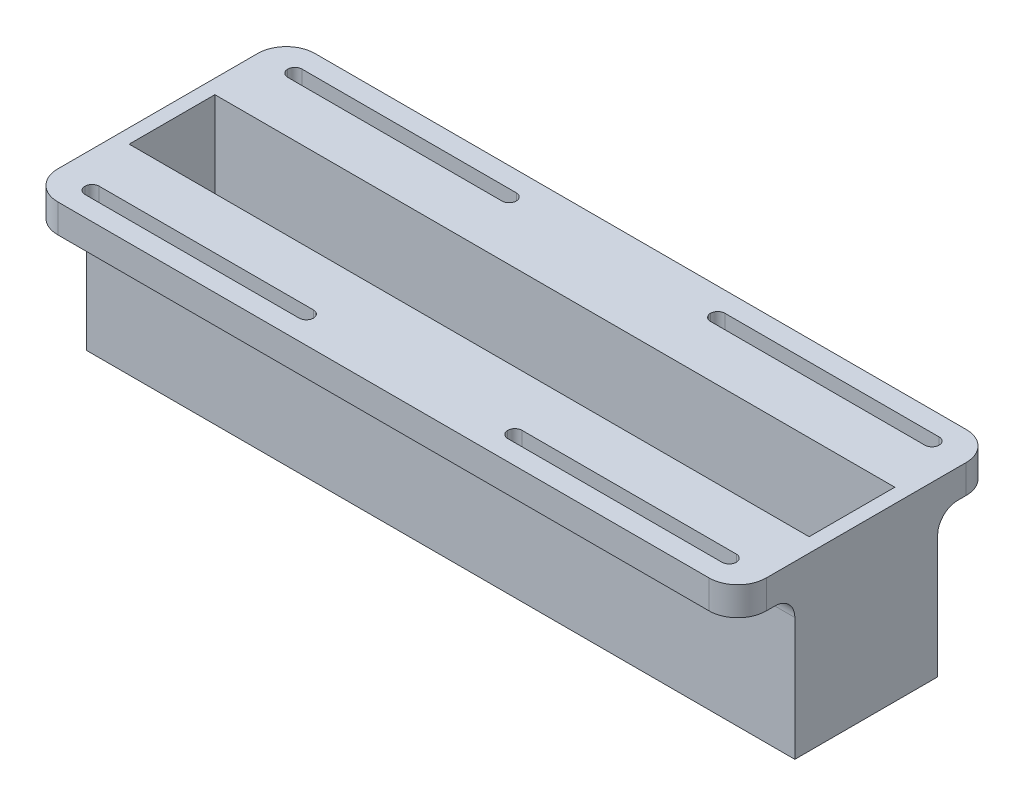
SolidWorks part; units mm, degrees
ref_plane "Plan de face" through (0, 0, 0) normal (0, 0, 1) x (1, 0, 0)
ref_plane "Plan de dessus" through (0, 0, 0) normal (0, 1, 0) x (1, 0, 0)
ref_plane "Plan de droite" through (0, 0, 0) normal (1, 0, 0) x (0, 0, -1)
sketch "Esquisse1" plane through (0, 0, 0) normal (0, 0, 1) x (1, 0, 0)
  line L1 (0, 0) -> (119, 0)
  line L2 (0, 0) -> (0, 61)
  line L3 (0, 61) -> (119, 61)
  line L4 (119, 0) -> (119, 61)
  line L5 (-2.5, -2.5) -> (121.5, -2.5)
  line L6 (-2.5, -2.5) -> (-2.5, 63.5)
  line L7 (-2.5, 63.5) -> (121.5, 63.5)
  line L8 (121.5, -2.5) -> (121.5, 63.5)
  dimension "D1" = 119
  dimension "D2" = 61
  dimension "D3" = 124
  dimension "D4" = 2.5
  dimension "D5" = 2.5
  dimension "D6" = 66
extrude "Boss.-Extru.1" add sketch "Esquisse1" along normal blind 15
sketch "Esquisse2" plane through (0, 0, 15) normal (0, 0, 1) x (1, 0, 0)
  line L0 (121.5, -2.5) -> (121.5, 63.5) construction
  line L1 (-2.5, -2.5) -> (121.5, -2.5)
  line L2 (-2.5, -2.5) -> (-2.5, 27.5)
  line L3 (-2.5, 27.5) -> (121.5, 27.5)
  line L4 (121.5, -2.5) -> (121.5, 27.5)
  line L6 (-2.5, 27.5) -> (121.5, 27.5)
  line L7 (-7.3247, 27.5) -> (134.2652, 27.5)
  line L8 (-7.3247, 27.5) -> (-7.3247, 70.1834)
  line L9 (-7.3247, 70.1834) -> (134.2652, 70.1834)
  line L10 (134.2652, 27.5) -> (134.2652, 70.1834)
  line M1 (121.5, -2.5) -> (121.5, 63.5)
  line M3 (121.5, 63.5) -> (-2.5, 63.5)
  line M5 (-2.5, 63.5) -> (-2.5, -2.5)
  line M7 (-2.5, -2.5) -> (121.5, -2.5)
  line M9 (0, 0) -> (0, 61)
  line M11 (0, 61) -> (119, 61)
  line M13 (119, 61) -> (119, 0)
  line M15 (119, 0) -> (0, 0)
  dimension "D1" = 30
extrude "Boss.-Extru.2" add sketch "Esquisse2" along normal blind 5 contours L3 M5 M7 M1 M13 M15 M9 | L2 L1 | L3 M9 M15 M13 | L1 L4 region at (-1.2242, 12.5, 15) region at (59.5, 13.75, 15)
sketch "Esquisse3" plane through (0, 0, 0) normal (0, 0, -1) x (-1, 0, 0)
  line L0 (-121.5, -2.5) -> (-121.5, 63.5) construction
  line L1 (-121.5, 27.5) -> (2.5, 27.5)
  line L2 (-121.5, 27.5) -> (-121.5, -2.5)
  line L3 (-121.5, -2.5) -> (2.5, -2.5)
  line L4 (2.5, 27.5) -> (2.5, -2.5)
extrude "Boss.-Extru.3" add sketch "Esquisse3" along normal blind 5
extrude "Enlèv. mat.-Extru.2" cut sketch "Esquisse2<4>" against normal through all contours L3 M5 M9 M11 M13 M1 M3 | L3 M9 M13 M11 | L7 L10 L9 L8 M5 M3 M1 region at (-1.2088, 45.5, 15) region at (-4.9123, 28.9788, 15) region at (59.5, 44.25, 15)
sketch "Esquisse2<4>" plane through (0, 0, 15) normal (0, 0, 1) x (1, 0, 0) same geometry as "Esquisse2"
sketch "Esquisse4" plane through (0, 0, 20) normal (0, 0, 1) x (1, 0, 0)
  line L0 (-2.5, 27.5) -> (121.5, 27.5) construction
  line L1 (-2.5, 27.5) -> (121.5, 27.5)
  line L2 (-2.5, 27.5) -> (-2.5, 22.5)
  line L3 (-2.5, 22.5) -> (121.5, 22.5)
  line L4 (121.5, 27.5) -> (121.5, 22.5)
  line L5 (121.5, -2.5) -> (121.5, 27.5) construction
  dimension "D1" = 5
extrude "Boss.-Extru.4" add sketch "Esquisse4" along normal blind 10
sketch "Esquisse6" plane through (0, 0, -5) normal (0, 0, -1) x (-1, 0, 0)
  line L0 (2.5, -2.5) -> (2.5, 27.5) construction
  line L1 (-121.5, 27.5) -> (2.5, 27.5)
  line L2 (-121.5, 27.5) -> (-121.5, 22.5)
  line L3 (-121.5, 22.5) -> (2.5, 22.5)
  line L4 (2.5, 27.5) -> (2.5, 22.5)
  dimension "D1" = 5
extrude "Boss.-Extru.5" add sketch "Esquisse6" along normal blind 10
sketch "Esquisse5" plane through (0, 27.5, 0) normal (0, 1, 0) x (1, 0, 0)
  line L0 (121.5, -30) -> (-2.5, -30) construction
  line L1 (2.5, -26.5) -> (116.5, -26.5)
  line L2 (2.5, -26.5) -> (2.5, -24)
  line L3 (2.5, -24) -> (116.5, -24)
  line L4 (116.5, -26.5) -> (116.5, -24)
  line L5 (-2.5, -30) -> (-2.5, 15) construction
  line L6 (121.5, -30) -> (121.5, 15) construction
  line L7 (-2.5, -30) -> (-2.5, 15) construction
  line L8 (42.5, -24) -> (76.5, -24)
  line L9 (42.5, -24) -> (42.5, -26.5)
  line L10 (42.5, -26.5) -> (76.5, -26.5)
  line L11 (76.5, -24) -> (76.5, -26.5)
  line L12 (2.5, 11.5) -> (116.5, 11.5)
  line L13 (2.5, 11.5) -> (2.5, 9)
  line L14 (2.5, 9) -> (116.5, 9)
  line L15 (116.5, 11.5) -> (116.5, 9)
  line L16 (121.5, -30) -> (121.5, 15) construction
  line L17 (-2.5, 15) -> (121.5, 15) construction
  line L18 (42.5, 11.5) -> (76.5, 11.5)
  line L19 (42.5, 11.5) -> (42.5, 9)
  line L20 (42.5, 9) -> (76.5, 9)
  line L21 (76.5, 11.5) -> (76.5, 9)
  dimension "D1" = 2.5
  dimension "D2" = 3.5
  dimension "D3" = 5
  dimension "D4" = 5
  dimension "D5" = 40
  dimension "D6" = 40
  dimension "D7" = 5
  dimension "D8" = 5
  dimension "D9" = 40
  dimension "D10" = 40
  dimension "D11" = 2.5
  dimension "D12" = 3.5
extrude "Enlèv. mat.-Extru.3" cut sketch "Esquisse5" against normal blind 10 contours L9 L3 L2 L1 | L3 L11 L1 L4 | L19 L12 L13 L14 | L12 L21 L14 L15 region at (22.5, 27.5, 25.25) region at (96.5, 27.5, 25.25) region at (22.5, 27.5, -10.25) region at (96.5, 27.5, -10.25)
fillet "Congé5" radius 5 4 edges at (121.5, 25, 30) (121.5, 25, -15) (-2.5, 25, -15) (-2.5, 25, 30)
fillet "Congé6" radius 3.5 2 edges
fillet "Congé7" radius 1.25 16 edges at (76.5, 25, -11.5) (76.5, 25, -9) (116.5, 25, -9) (116.5, 25, -11.5) (42.5, 25, -11.5) (42.5, 25, -9) (2.5, 25, -11.5) (2.5, 25, -9) (2.5, 25, 24) (2.5, 25, 26.5) (42.5, 25, 24) (42.5, 25, 26.5) (76.5, 25, 24) (76.5, 25, 26.5) (116.5, 25, 24) (116.5, 25, 26.5)
sketch "Esquisse7" plane through (0, 0, 0) normal (0, 1, 0) x (1, 0, 0)
  line L0 (0, -15) -> (119, -15) construction
  line L1 (114, 0) -> (79, 0)
  line L2 (114, 0) -> (114, -15)
  line L3 (114, -15) -> (79, -15)
  line L4 (79, 0) -> (79, -15)
  line L5 (119, -15) -> (119, 0) construction
  dimension "D1" = 5
  dimension "D2" = 40
extrude "Enlèv. mat.-Extru.4" cut sketch "Esquisse7" against normal through all
